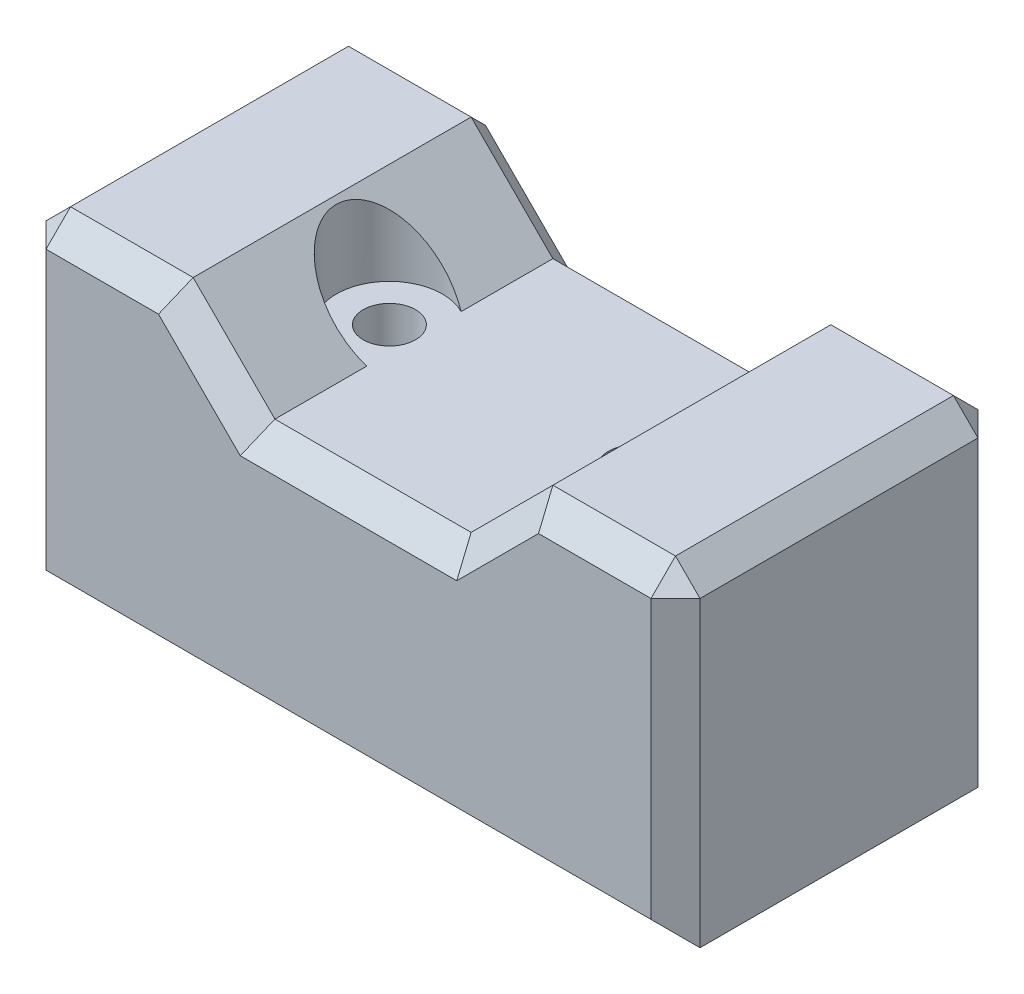
SolidWorks part; units mm, degrees
ref_plane "Front" through (0, 0, 0) normal (0, 0, 1) x (1, 0, 0)
ref_plane "Top" through (0, 0, 0) normal (0, 1, 0) x (1, 0, 0)
ref_plane "Right" through (0, 0, 0) normal (1, 0, 0) x (0, 0, -1)
sketch "草图1" plane through (0, 0, 0) normal (0, 1, 0) x (1, 0, 0)
  line L0 (0, 0) -> (7.5, 0) construction
  line L1 (-20, -10) -> (20, -10)
  line L2 (-20, -10) -> (-20, 10)
  line L3 (-20, 10) -> (20, 10)
  line L4 (20, -10) -> (20, 10)
  line L5 (-20, -10) -> (20, 10) construction
  line L6 (-20, 10) -> (20, -10) construction
  line L7 (0, 0) -> (0, 10) construction
  circle A0 centre (7.5, 0) radius 1.6
  circle A1 centre (-7.5, 0) radius 1.6
  point P0 (0, 0)
  dimension "D3" = 7.5
  dimension "D4" = 3.2
  dimension "D1" = 20
  dimension "D2" = 40
extrude "凸台-拉伸1" add sketch "草图1" along normal blind 20
sketch "草图2" plane through (0, 0, 10) normal (0, 0, 1) x (1, 0, 0)
  line L0 (0, 20) -> (0, 15) construction
  line L1 (-20, 20) -> (20, 20) construction
  line L2 (-6, 15) -> (6, 15)
  line L3 (6, 15) -> (11, 20)
  line L4 (-6, 15) -> (-11, 20)
  line L5 (-11, 20) -> (11, 20)
  dimension "D1" = 5
  dimension "D2" = 6
  dimension "D3" = 135
extrude "切除-拉伸1" cut sketch "草图2" against normal blind 20
sketch "草图3" plane through (0, 20, 0) normal (0, 1, 0) x (1, 0, 0)
  circle A0 centre (7.5, 0) radius 3.25
  circle A1 centre (-7.5, 0) radius 3.25
  dimension "D1" = 6.5
  dimension "D2" = 6.5
extrude "切除-拉伸2" cut sketch "草图3" against normal up to surface (5 mm away) up to face at (0, 15, 0)
chamfer "倒角1" distance 1.5 angle 45 18 edges at (8.5, 17.5, 10) (15.5, 20, 10) (20, 10, 10) (0, 0, 10) (-20, 10, 10) (0, 15, 10) (-8.5, 17.5, 10) (-15.5, 20, 10) (-20, 10, -10) (0, 0, -10) (20, 10, -10) (20, 20, 0) (15.5, 20, -10) (8.5, 17.5, -10) (0, 15, -10) (-8.5, 17.5, -10) (-15.5, 20, -10) (-20, 20, 0)
